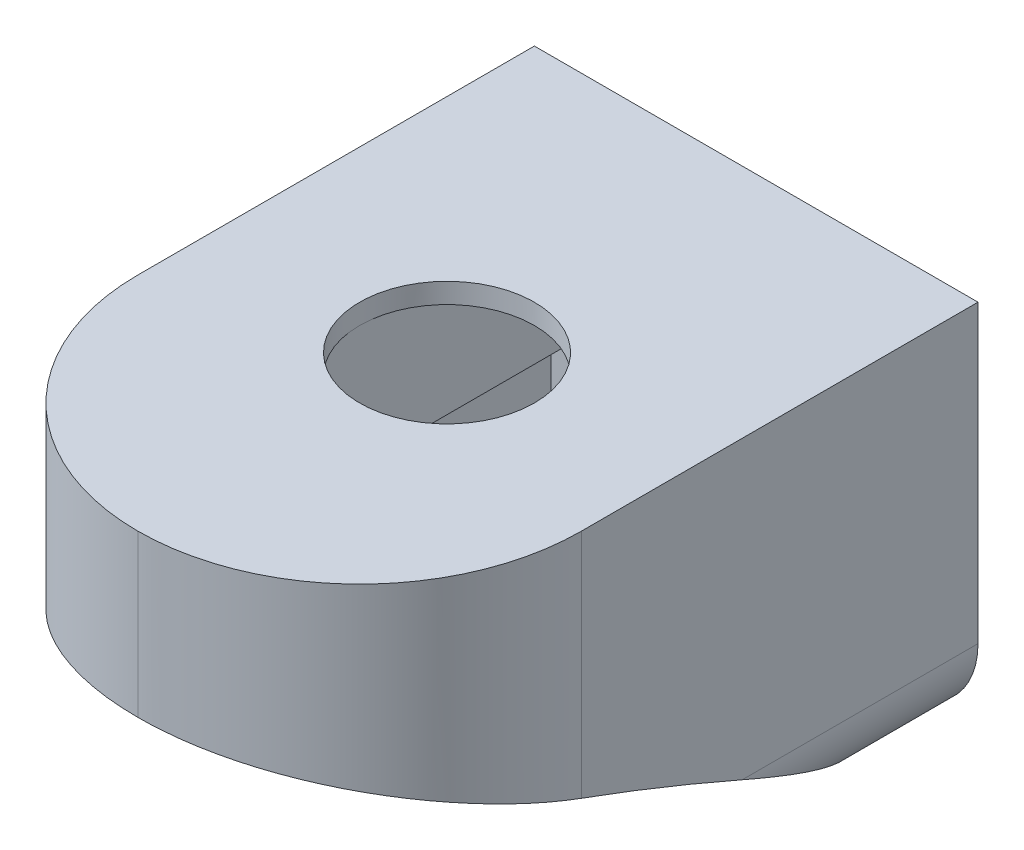
SolidWorks part; units mm, degrees
ref_plane "Front Plane" through (0, 0, 0) normal (0, 0, 1) x (1, 0, 0)
ref_plane "Top Plane" through (0, 0, 0) normal (0, 1, 0) x (1, 0, 0)
ref_plane "Right Plane" through (0, 0, 0) normal (1, 0, 0) x (0, 0, -1)
sketch "Sketch1" plane through (0, 0, 0) normal (0, 0, 1) x (1, 0, 0)
  line L1 (-16.5, 14) -> (16.5, 14)
  line L2 (-16.5, 14) -> (-16.5, -14)
  line L3 (-16.5, -14) -> (16.5, -14)
  line L4 (16.5, 14) -> (16.5, -14)
  line L5 (-16.5, 14) -> (16.5, -14) construction
  line L6 (-16.5, -14) -> (16.5, 14) construction
  point P0 (0, 0)
  dimension "D1" = 33
  dimension "D2" = 28
extrude "Boss-Extrude1" add sketch "Sketch1" along normal blind 46
sketch "Sketch2" plane through (16.5, 0, 0) normal (1, 0, 0) x (0, 0, -1)
  line L0 (-46, 2) -> (-46, -14)
  line L1 (-46, -14) -> (-46, 14) construction
  line L2 (-46, -14) -> (-5, -14)
  line L3 (-46, -14) -> (0, -14) construction
  spline S0 degree 2 poles (-5, -14) (-24.7518, -3.724) (-46, 2) knots 0 0 0 1 1 1
  point P8 (-46, 2)
  dimension "D1" = 12
  dimension "D2" = 5
extrude "Cut-Extrude1" cut sketch "Sketch2" against normal blind 46
sketch "Sketch3" plane through (16.5, 0, 0) normal (1, 0, 0) x (0, 0, -1)
  line L0 (-5, -14) -> (-1.7691, -14)
  line L1 (-5, -14) -> (0, -14) construction
  line L2 (-1.7691, -14) -> (-1.7691, 3.5)
  line L3 (-1.7691, 3.5) -> (-39.7691, 3.5)
  line L4 (-39.7691, 3.5) -> (-39.7691, 0.2138)
  parabola Q0 (-5, -14) -> (-46, 2) focus (-66.9367, -96.8693) apex (-35.4694, -1.1465) construction
  parabola Q1 (-5, -14) -> (-46, 2) focus (-66.9367, -96.8693) apex (-35.4694, -1.1465) construction
  parabola Q2 (-5, -14) -> (-39.7691, 0.2138) focus (-66.9367, -96.8693) apex (-35.4694, -1.1465)
  dimension "D1" = 38
  dimension "D2" = 17.5
extrude "Cut-Extrude2" cut sketch "Sketch3" against normal blind 27 from offset 3 offset against normal yes
fillet "Fillet2" radius 12.5 2 edges at (13.5, 1.8569, 39.7691) (-13.5, 1.8569, 39.7691)
fillet "Fillet3" radius 16.5 2 edges at (16.5, 8, 46) (-16.5, 8, 46)
fillet "Fillet4" radius 6 2 edges at (-16.5, -14, 2.5) (16.5, -14, 2.5)
sketch "Sketch4" plane through (0, 3.5, 0) normal (0, -1, 0) x (1, 0, 0)
  line L0 (0, 0) -> (0, 28.0279) construction
  line L1 (-10.5, 0) -> (10.5, 0) construction
  line L2 (-6.5, 29.5) -> (6.5, 29.5)
  line L3 (-6.5, 29.5) -> (-6.5, 6.5)
  line L4 (-6.5, 6.5) -> (6.5, 6.5)
  line L5 (6.5, 29.5) -> (6.5, 6.5)
  line L6 (-6.5, 29.5) -> (6.5, 6.5) construction
  line L7 (-6.5, 6.5) -> (6.5, 29.5) construction
  point P2 (0, 18)
  dimension "D1" = 23
  dimension "D2" = 6.5
  dimension "D3" = 13
extrude "Cut-Extrude3" cut sketch "Sketch4" against normal blind 9
sketch "Sketch5" plane through (0, 12.5, 0) normal (0, -1, 0) x (1, 0, 0)
  line L0 (6.5, 29.5) -> (-6.5, 29.5) construction
  circle A0 centre (0, 23) radius 6.5
  dimension "D1" = 13
extrude "Cut-Extrude4" cut sketch "Sketch5" against normal through all
sketch "Sketch6" plane through (0, 3.5, 0) normal (0, -1, 0) x (1, 0, 0)
  line L0 (-6.5, 18) -> (6.5, 18) construction
  line L1 (-6.5, 29.5) -> (-6.5, 6.5) construction
  line L2 (6.5, 6.5) -> (6.5, 29.5) construction
  circle A0 centre (0, 31.8) radius 1
  circle A1 centre (0, 4.2) radius 1
  dimension "D1" = 13.8
  dimension "D3" = 2
  dimension "D4" = 2
  dimension "D2" = 13.8
extrude "Cut-Extrude5" cut sketch "Sketch6" against normal blind 8
sketch "Sketch7" plane through (0, 0, 0) normal (0, 0, -1) x (-1, 0, 0)
  line L0 (0, 0) -> (-22.9815, 0) construction
  line L1 (-16.5, -8) -> (-16.5, 14) construction
  circle A0 centre (-9.5, 0) radius 1.3
  circle A1 centre (-5, 0) radius 2.5
  circle A2 centre (-0.5, 0) radius 1.3
  point P11 (-5.4847, -0.3759)
  dimension "D1" = 5
  dimension "D2" = 2.6
  dimension "D3" = 2.6
  dimension "D4" = 4.5
  dimension "D5" = 4.5
  dimension "D6" = 11.5
extrude "Cut-Extrude6" cut sketch "Sketch7" against normal up to surface (1.7691 mm away) up to face at (0, -7.9645, 1.7691)
